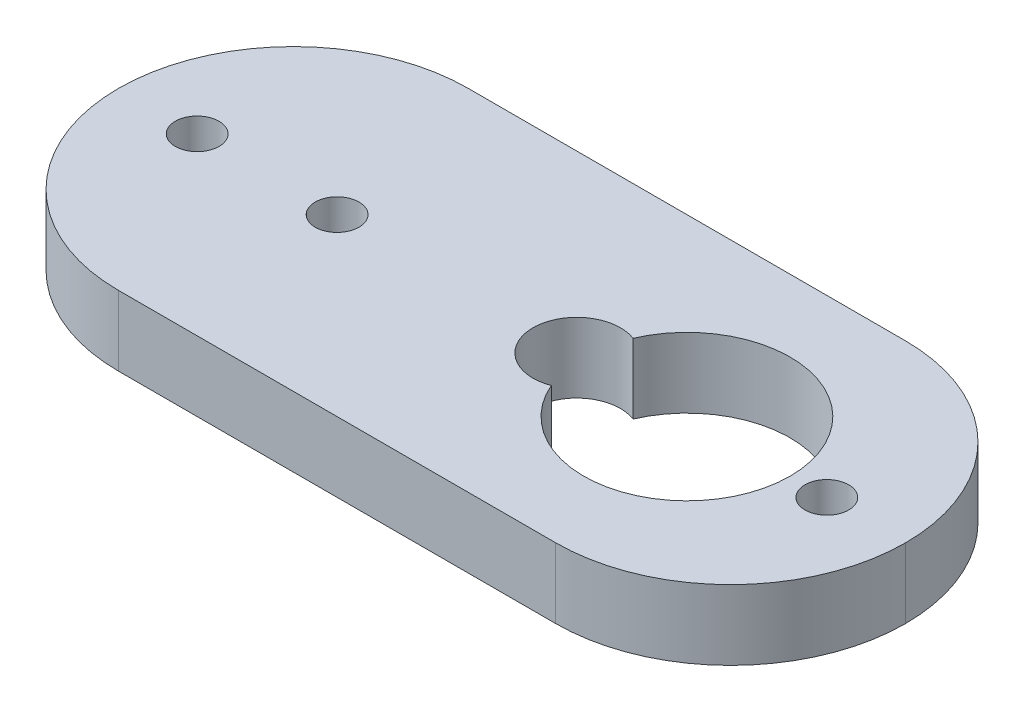
SolidWorks part; units mm, degrees
ref_plane "Front Plane" through (0, 0, 0) normal (0, 0, 1) x (1, 0, 0)
ref_plane "Top Plane" through (0, 0, 0) normal (0, 1, 0) x (1, 0, 0)
ref_plane "Right Plane" through (0, 0, 0) normal (1, 0, 0) x (0, 0, -1)
sketch "Sketch1" plane through (0, 0, 0) normal (0, 1, 0) x (1, 0, 0)
  line L1 (22.5, -10) -> (-22.5, -10)
  line L2 (22.5, -10) -> (22.5, 10)
  line L3 (22.5, 10) -> (-22.5, 10)
  line L4 (-22.5, -10) -> (-22.5, 10)
  line L5 (22.5, -10) -> (-22.5, 10) construction
  line L6 (22.5, 10) -> (-22.5, -10) construction
  point P0 (0, 0)
  dimension "D1" = 20
  dimension "D2" = 45
extrude "Boss-Extrude1" add sketch "Sketch1" along normal blind 4
sketch "Sketch2" plane through (0, 4, 0) normal (0, 1, 0) x (1, 0, 0)
  arc A0 (4.5833, -2.3387) -> (4.5833, 2.3387) centre (10, 0) ccw
  circle A1 centre (18, 0) radius 1.25
  circle A2 centre (-10, 0) radius 1.25
  circle A3 centre (-18, 0) radius 1.25
  arc A4 (4.5833, 2.3387) -> (4.5833, -2.3387) centre (3.7, 0) ccw
  dimension "D1" = 11.8
  dimension "D3" = 2.5
  dimension "D4" = 8
  dimension "D5" = 2.5
  dimension "D6" = 20
  dimension "D7" = 2.5
  dimension "D8" = 8
  dimension "D9" = 6.3
  dimension "D10" = 5
  dimension "D2" = 10
extrude "Cut-Extrude1" cut sketch "Sketch2" against normal through all
fillet "Fillet2" radius 10 4 edges at (-22.5, 2, -10) (22.5, 2, -10) (-22.5, 2, 10) (22.5, 2, 10)
